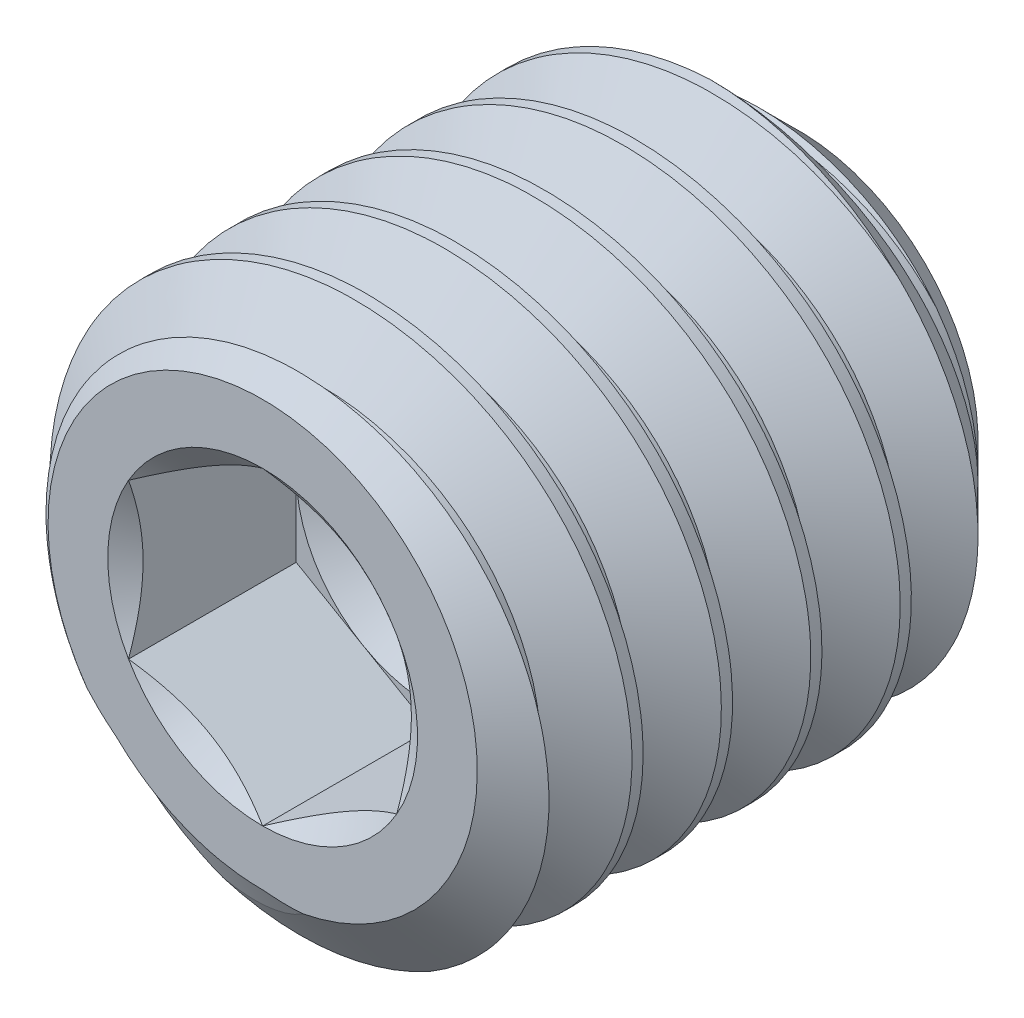
SolidWorks part; units mm, degrees
ref_plane "Front" through (0, 0, 0) normal (0, 0, 1) x (1, 0, 0)
ref_plane "Top" through (0, 0, 0) normal (0, 1, 0) x (1, 0, 0)
ref_plane "Right" through (0, 0, 0) normal (1, 0, 0) x (0, 0, -1)
sketch "Sketch22" plane through (0, 0, 0) normal (1, 0, 0) x (0, 0, -1)
  line L0 (-1.5, 0) -> (-1.5, 1.2)
  line L1 (-1.5, 1.2) -> (-1.2899, 1.5)
  line L2 (-1.2899, 1.5) -> (1, 1.5)
  line L3 (1, 1.5) -> (1.5, 1)
  line L4 (-0.145, 1.5) -> (-0.145, -1.5) construction
  line L5 (1.5, 0) -> (-1.5, 0)
  line L6 (-1.5, 1.2) -> (-1.5, -1.2) construction
  line L7 (1.5, 0) -> (1.5, 1)
  point P11 (-0.145, 0)
  dimension "Length" = 3
  dimension "D3" = 35
  dimension "D6" = 45
  dimension "Dia" = 3
  dimension "D1" = 2.4
  dimension "D2" = 0.5
revolve "Revolve1" add sketch "Sketch22" angle 360 about L5
ref_plane "Plane1" through (0, 0, -1.5) normal (0, 0, 1) x (1, 0, 0)
sketch "Sketch27" plane through (0, 0, -1.5) normal (0, 0, 1) x (1, 0, 0)
  circle A0 centre (0, 0) radius 1.5 construction
  circle A1 centre (0, 0) radius 1.5
curve "Helix/Spiral1" pitch 0.5 height 3.5 radius 1.5 centre (0, 0, -1.5) axis (0, 0, 1) start towards (0, 1, 0)
sketch "Sketch28" plane through (0, 0, 0) normal (1, 0, 0) x (0, 0, -1)
  line L0 (1.5, 1.5) -> (1.9375, 1.5)
  line L1 (1.9375, 1.5) -> (1.75, 1.1752)
  line L2 (1.75, 1.1752) -> (1.6875, 1.1752)
  line L3 (1.6875, 1.1752) -> (1.5, 1.5)
  line L4 (1.5938, 1.3376) -> (1.8438, 1.3376) construction
  line L6 (-1.2899, 1.5) -> (1, 1.5) construction
  dimension "D1" = 0.0625
  dimension "D3" = 60
  dimension "D2" = 0.25
sweep "Cut-Sweep2" cut profiles "Sketch28" path "Helix/Spiral1" align with end faces yes
sketch "Sketch23" plane through (0, 0, 1.5) normal (0, 0, 1) x (1, 0, 0)
  line L1 (0, 0.866) -> (-0.75, 0.433)
  line L2 (-0.75, 0.433) -> (-0.75, -0.433)
  line L3 (-0.75, -0.433) -> (0, -0.866)
  line L4 (0, -0.866) -> (0.75, -0.433)
  line L5 (0.75, -0.433) -> (0.75, 0.433)
  line L6 (0.75, 0.433) -> (0, 0.866)
  circle A0 centre (0, 0) radius 0.75 construction
  dimension "Hex" = 1.5
extrude "Cut-Extrude10" cut sketch "Sketch23" against normal blind 0.9375
sketch "Sketch24" plane through (0, 0, 1.5) normal (0, 0, 1) x (1, 0, 0)
  circle A0 centre (0, 0) radius 0.866
extrude "Cut-Extrude11" cut sketch "Sketch24" against normal through all draft 55
sketch "Sketch26" plane through (0, 0, 0.5625) normal (0, 0, 1) x (1, 0, 0)
  circle A0 centre (0, 0) radius 0.75 construction
  circle A1 centre (0, 0) radius 0.75
extrude "Cut-Extrude12" cut sketch "Sketch26" against normal through all draft 60
sketch "Sketch30" plane through (0, 0, 0) normal (1, 0, 0) x (0, 0, -1)
  line L0 (-1.2899, 1.5) -> (1, 1.5) construction
  line L1 (-1.5, 0) -> (-1.5, 1.2) construction
  line L2 (1.5, 0) -> (1.5, 1) construction
  point P0 (-1.5, 1.5)
  point P1 (1.5, 1.5)
  point P2 (1.5, -1.5)
  point P11 (0.25, -1.5)
  dimension "D1" = 1.25
equation "\"D1@Sketch28\" = \"D4@Helix/Spiral1\" * .125"
equation "\"D2@Sketch28\" = \"D4@Helix/Spiral1\" * .5"
equation "\"D3@Helix/Spiral1\" = \"Length@Sketch22\" + \"D4@Helix/Spiral1\""
equation "\"D1@Sketch30\" = \"D4@Helix/Spiral1\" * 2.5"
equation "\"hex Depth@Cut-Extrude10\" = \"Hex@Sketch23\" * .625"
equation "\"D1@Sketch22\" = \"Dia@Sketch22\" * .8"
equation "\"D2@Sketch22\" = \"D4@Helix/Spiral1\""
